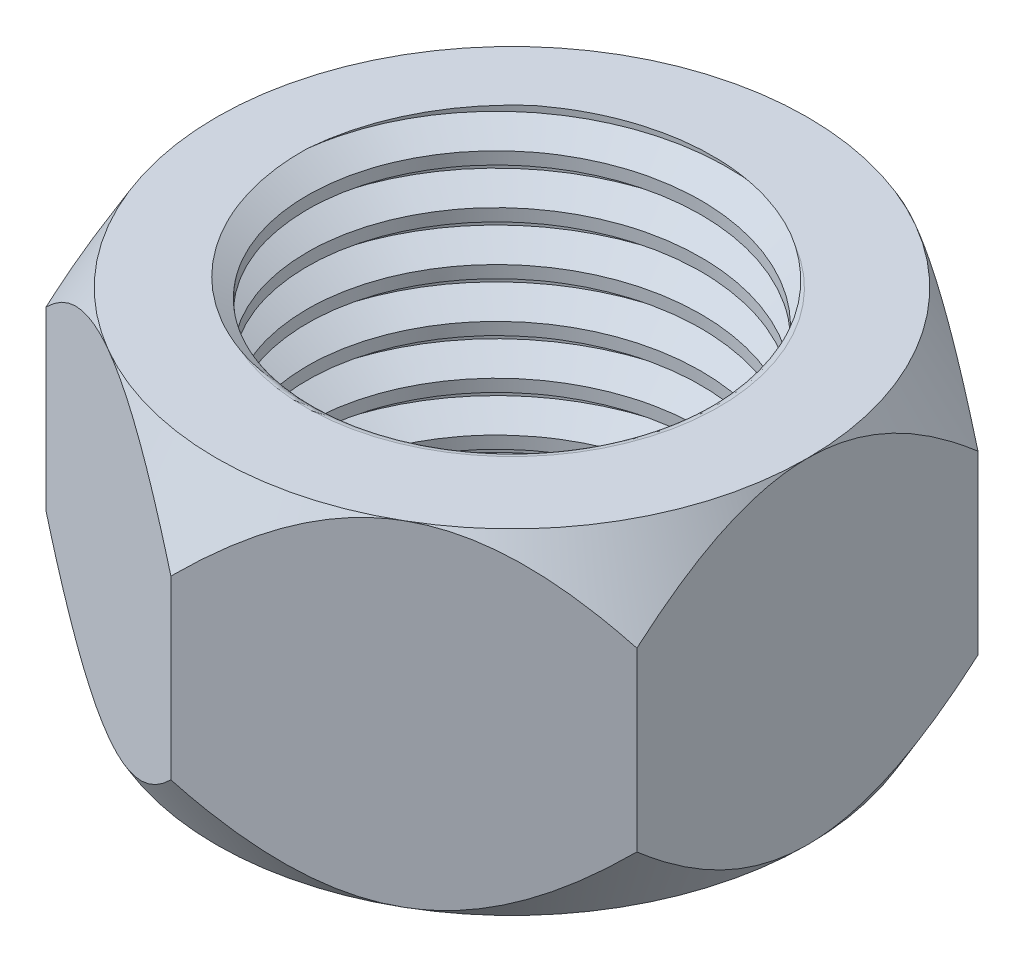
SolidWorks part; units mm, degrees
ref_plane "Front Plane" through (0, 0, 0) normal (0, 0, 1) x (1, 0, 0)
ref_plane "Top Plane" through (0, 0, 0) normal (0, 1, 0) x (1, 0, 0)
ref_plane "Right Plane" through (0, 0, 0) normal (1, 0, 0) x (0, 0, -1)
sketch "Sketch1" plane through (0, 0, 0) normal (0, 1, 0) x (1, 0, 0)
  line L1 (0, 17.3205) -> (-15, 8.6603)
  line L2 (-15, 8.6603) -> (-15, -8.6603)
  line L3 (-15, -8.6603) -> (0, -17.3205)
  line L4 (0, -17.3205) -> (15, -8.6603)
  line L5 (15, -8.6603) -> (15, 8.6603)
  line L6 (15, 8.6603) -> (0, 17.3205)
  circle A0 centre (0, 0) radius 15 construction
  dimension "D1" = 15
extrude "Boss-Extrude1" add sketch "Sketch1" along normal blind 17
sketch "Sketch2" plane through (0, 17, 0) normal (0, 1, 0) x (1, 0, 0)
  circle A0 centre (0, 0) radius 15
extrude "Cut-Extrude1" cut sketch "Sketch2" against normal blind 10 draft 30 flip side to cut
sketch "Sketch3" plane through (0, 0, 0) normal (0, -1, 0) x (1, 0, 0)
  circle A0 centre (0, 0) radius 15
extrude "Cut-Extrude2" cut sketch "Sketch3" against normal blind 10 draft 30 flip side to cut
sketch "Sketch4" plane through (0, 0, 0) normal (0, -1, 0) x (1, 0, 0)
  circle A0 centre (0, 0) radius 10
  dimension "D1" = 20
extrude "Cut-Extrude3" cut sketch "Sketch4" against normal through all
fillet "Fillet1" radius 0.5 2 edges at (0, 17, -10) (0, 0, -10)
thread "Thread1" pitch 2.5 method cut profile "Thread Profile1" start angle 0, offset 3, length 0, pitch 2.5, diameter 20
ref_plane "Plane1" through (10, -2.5, 0) normal (0, 0, 1) x (1, 0, 0)
sketch "Thread Profile1" plane through (10, -2.5, 0) normal (0, 0, 1) x (1, 0, 0)
  line L0 (0, 0) -> (0, 2.5) construction
  line L1 (0, 0) -> (1.3532, 0.7812)
  line L2 (1.3532, 0.7812) -> (1.3532, 1.0937)
  line L3 (1.3532, 1.0937) -> (0, 1.875)
  line L4 (1.3532, 0.9375) -> (0, 0.9375) construction
  line L11 (0, 0) -> (0, 1.875)
  point P2 (0, 0)
  dimension "Pitch" = 2.5
  dimension "Profile_Angle" = 60
  dimension "Profile_Land" = 0.3125
  dimension "Profile_Height" = 1.3532
